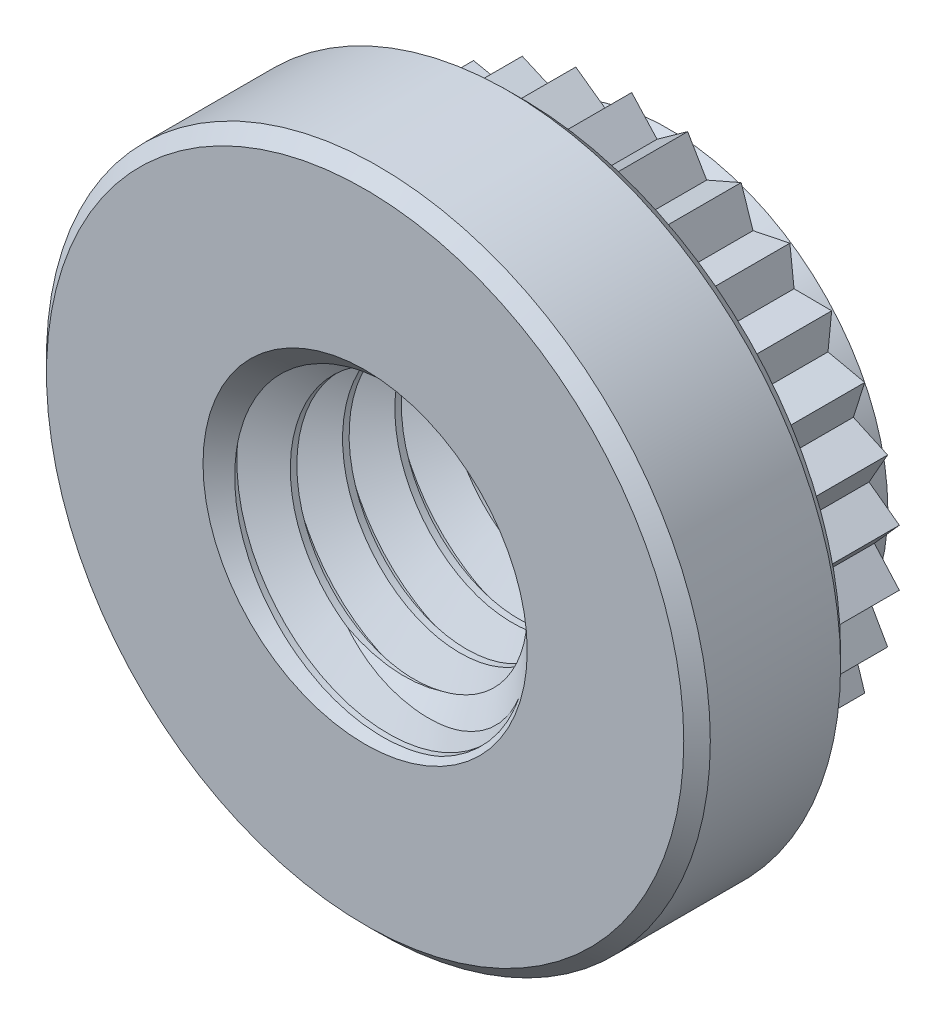
SolidWorks part; units mm, degrees
ref_plane "Front Plane" through (0, 0, 0) normal (0, 0, 1) x (1, 0, 0)
ref_plane "Top Plane" through (0, 0, 0) normal (0, 1, 0) x (1, 0, 0)
ref_plane "Right Plane" through (0, 0, 0) normal (1, 0, 0) x (0, 0, -1)
sketch "Sketch1" plane through (0, 0, 0) normal (0, 0, 1) x (1, 0, 0)
  circle A0 centre (0, 0) radius 3.175
  dimension "A" = 6.35
extrude "Extrude1" add sketch "Sketch1" against normal blind 1.5
sketch "Sketch15" plane through (0, 0, -1.5) normal (0, 0, -1) x (-1, 0, 0)
  circle A0 centre (0, 0) radius 2.1
  dimension "hole dia" = 4.2
sketch "Sketch2" plane through (0, 0, -1.5) normal (0, 0, -1) x (-1, 0, 0)
  circle A0 centre (0, 0) radius 2.1125
  dimension "D1" = 4.225
extrude "Extrude2" add sketch "Sketch2" along normal blind 1.4
sketch "Sketch5" plane through (0, 0, -2.9) normal (0, 0, -1) x (-1, 0, 0)
  circle A0 centre (0, 0) radius 3.175 construction
  circle A3 centre (0, 0) radius 2.1
  dimension "C" = 4.2
extrude "Cut-Extrude1" cut sketch "Sketch5" against normal blind 0.35 draft 20 flip side to cut draft outward yes
chamfer "Chamfer2" distance 0.127 angle 45 2 edges at (3.175, 0, 0) (3.175, 0, -1.5)
sketch "Sketch7" plane through (0, 0, 0) normal (0, 0, 1) x (1, 0, 0)
  circle A0 centre (0, 0) radius 1.5
  dimension "Thread Od" = 3
extrude "Cut-Extrude3" cut sketch "Sketch7" against normal through all
sketch "Sketch8" plane through (0, 0, -2.9) normal (0, 0, -1) x (-1, 0, 0)
  circle A0 centre (0, 0) radius 1.5 construction
  circle A1 centre (0, 0) radius 1.5
curve "Helix/Spiral1" pitch 0.5 height 4.9 radius 1.5 centre (0, 0, -2.9) axis (0, 0, 1) start towards (0, 1, 0) parameters "pitch"=0.5
sketch "Sketch9" plane through (0, 0, 0) normal (1, 0, 0) x (0, 0, -1)
  line L0 (3.3375, 1.5) -> (3.15, 1.1752)
  line L1 (3.15, 1.1752) -> (3.0875, 1.1752)
  line L2 (3.0875, 1.1752) -> (2.9, 1.5)
  line L3 (3.3375, 1.5) -> (2.9, 1.5)
  line L4 (3.1187, 1.5) -> (3.1187, 1.1752) construction
  line L5 (3.2437, 1.3376) -> (2.9937, 1.3376) construction
  line L6 (2.9, -1.5) -> (2.9, 1.5) construction
  dimension "D1" = 60
  dimension "D2" = 0.0625
  dimension "D3" = 0.25
sweep "Sweep1" add profiles "Sketch9" path "Helix/Spiral1"
sketch "Sketch10" plane through (0, 0, 0) normal (0, 0, 1) x (1, 0, 0)
  circle A0 centre (0, 0) radius 3.175 construction
  circle A1 centre (0, 0) radius 3.175
extrude "Cut-Extrude4" cut sketch "Sketch10" along normal through all
sketch "Sketch11" plane through (0, 0, -2.9) normal (0, 0, -1) x (-1, 0, 0)
  circle A1 centre (0, 0) radius 2.1 construction
  circle A2 centre (0, 0) radius 2.1
extrude "Cut-Extrude5" cut sketch "Sketch11" along normal through all
sketch "Sketch13" plane through (0, 0, 0) normal (0, 0, 1) x (1, 0, 0)
  circle A2 centre (0, 0) radius 1.5508
  circle A3 centre (0, 0) radius 1.5508
  dimension "D1" = 0.0508
extrude "Cut-Extrude6" cut sketch "Sketch13" against normal through all draft 45
sketch "Sketch14" plane through (0, 0, -2.9) normal (0, 0, -1) x (-1, 0, 0)
  circle A2 centre (0, 0) radius 1.5635
  circle A3 centre (0, 0) radius 1.5635
  dimension "D1" = 0.0635
extrude "Cut-Extrude7" cut sketch "Sketch14" against normal through all draft 45
sketch "Sketch16" plane through (0, 0, -2.55) normal (0, 0, -1) x (-1, 0, 0)
  line L0 (0, 2.1) -> (0, 3.048) construction
  line L1 (0, 2.574) -> (-0.4694, 2.0597)
  line L2 (0, 2.574) -> (0.4694, 2.0597)
  circle A0 centre (0, 0) radius 1.9726 construction
  circle A1 centre (0, 0) radius 2.1 construction
  circle A2 centre (0, 0) radius 3.048 construction
  circle A3 centre (0, 0) radius 2.1125 construction
  arc A4 (-0.4694, 2.0597) -> (0.4694, 2.0597) centre (0, 0) cw
  circle A5 centre (0, 0) radius 2.1125 construction
  point P2 (0, 2.574)
  dimension "D2" = 0.9389
extrude "Boss-Extrude1" add sketch "Sketch16" against normal up to surface (1.05 mm away) up to face at (3.048, 0, -1.5)
pattern_circular "CirPattern4" count 30 over 360 about axis through (0, 0, -2.9) along (0, 0, -1) of "Boss-Extrude1"
equation "\"D3@Helix/Spiral1\"=\"B@Extrude1\"+\"panel min.@Extrude2\"+2"
equation "\"D2@Sketch9\" = \"pitch@Helix/Spiral1\"*.125"
equation "\"D3@Sketch9\" = \"pitch@Helix/Spiral1\"*.50"
equation "\"D1@Sketch2\" = \"hole dia@Sketch15\"+.025"
equation "\"D1@Cut-Extrude1\" = \"panel min.@Extrude2\"*.25"
equation "\"D2@Sketch16\"=\"D1@Sketch2\"/4.5"
equation "\"D1@CirPattern4\"=360/12"
